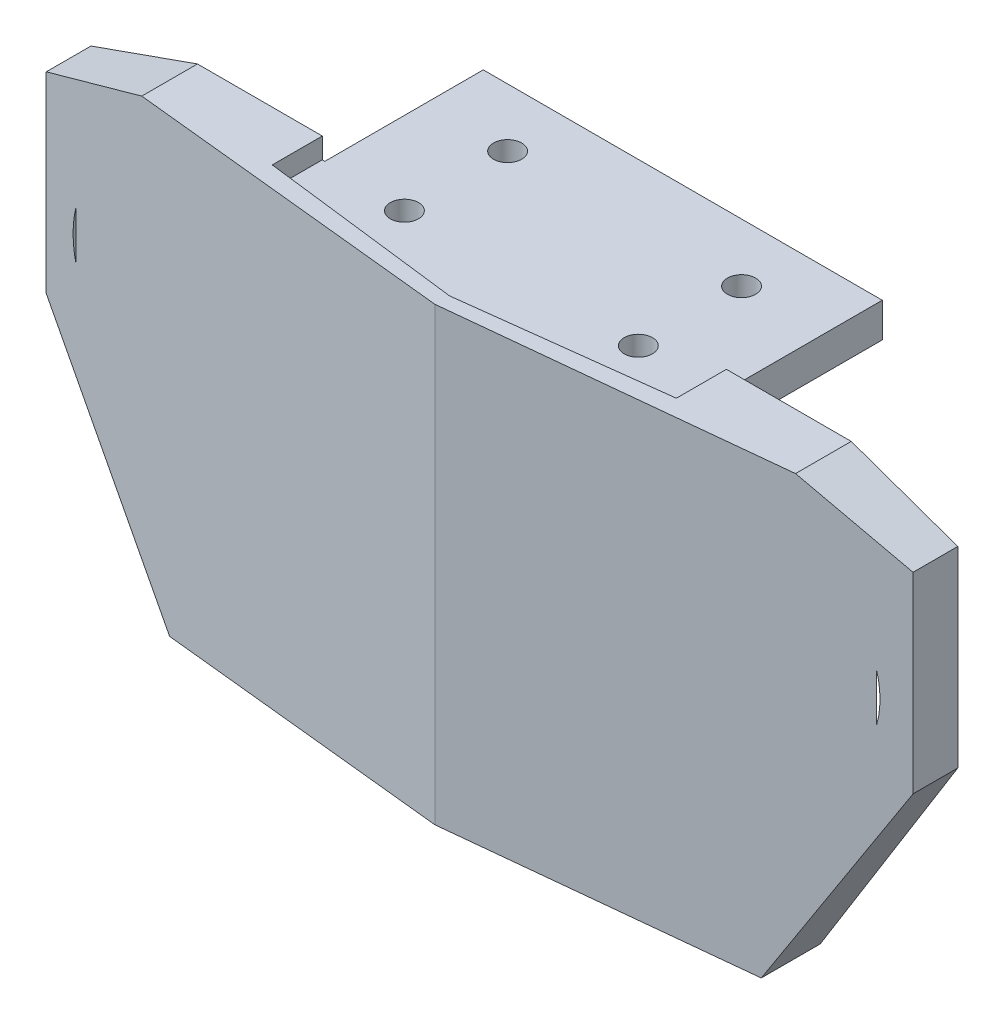
SolidWorks part; units mm, degrees
material "petg 20%"
ref_plane "Front Plane" through (0, 0, 0) normal (0, 0, 1) x (1, 0, 0)
ref_plane "Top Plane" through (0, 0, 0) normal (0, 1, 0) x (1, 0, 0)
ref_plane "Right Plane" through (0, 0, 0) normal (1, 0, 0) x (0, 0, -1)
sketch "Sketch1" plane through (0, 0, 0) normal (0, 0, 1) x (1, 0, 0)
  line L1 (-100, 30) -> (100, 30)
  line L2 (-100, 30) -> (-100, -30)
  line L3 (-100, -30) -> (100, -30)
  line L4 (100, 30) -> (100, -30)
  line L5 (-100, 30) -> (100, -30) construction
  line L6 (-100, -30) -> (100, 30) construction
  point P0 (0, 0)
  dimension "D1" = 200
  dimension "D2" = 60
extrude "Boss-Extrude1" add sketch "Sketch1" along normal blind 25
sketch "Sketch3" plane through (0, 0, 0) normal (0, 0, -1) x (-1, 0, 0)
  circle A0 centre (-45, 0) radius 13.65
  circle A1 centre (45, 0) radius 13.65
  dimension "D1" = 27.3
  dimension "D2" = 27.3
  dimension "D3" = 45
  dimension "D4" = 45
extrude "Cut-Extrude1" cut sketch "Sketch3" against normal blind 7
sketch "Sketch6" plane through (0, 0, 0) normal (0, 0, -1) x (-1, 0, 0)
  line L0 (0, 53.6444) -> (0, -51.0008) construction
  line L1 (-87.0208, 30) -> (-100, 15.5316)
  line L2 (-100, 30) -> (100, 30) construction
  line L3 (-100, -30) -> (-100, 30) construction
  line L4 (-100, -15.0909) -> (-89.0035, -30)
  line L5 (100, -30) -> (-100, -30) construction
  line L9 (100, -15.0909) -> (89.0035, -30)
  line L10 (87.0208, 30) -> (100, 15.5316)
  line L11 (-100, -15.0909) -> (-100, -30)
  line L12 (-100, -30) -> (-89.0035, -30)
  line L15 (-100, 15.5316) -> (-100, 30)
  line L16 (-100, 30) -> (-87.0208, 30)
  line L17 (87.0208, 30) -> (100, 30)
  line L18 (100, 30) -> (100, 15.5316)
  line L19 (89.0035, -30) -> (100, -30)
  line L20 (100, -30) -> (100, -15.0909)
extrude "Cut-Extrude3" cut sketch "Sketch6" against normal through all contours L16 L1 L15 | L12 L4 L11 | L20 L9 L19 | L18 L10 L17
ref_plane "Plane1" through (0, 0, 0) normal (1, 0, 0) x (0, 0, -1)
sketch "Sketch11" plane through (0, 0, 0) normal (0, 0, -1) x (-1, 0, 0)
  line L1 (-87.0208, 30) -> (87.0208, 30) construction
  line L3 (8.0014, 30) -> (-99.0282, 30)
  line L5 (8.0014, 24.58) -> (-99.0282, 24.58)
  line L6 (-99.0282, 30) -> (-99.0282, 24.58)
  line L7 (8.0014, 30) -> (98.3846, 30)
  line L9 (8.0014, 24.58) -> (98.3846, 24.58)
  line L10 (98.3846, 30) -> (98.3846, 24.58)
extrude "Cut-Extrude7" cut sketch "Sketch11" against normal blind 45
fillet "Fillet8" radius 5 8 edges at (100, 0.2203, 25) (94.5018, -22.5455, 25) (0, -30, 25) (-94.5018, -22.5455, 25) (-100, 0.2203, 25) (95.9414, 20.0558, 25) (-95.9414, 20.0558, 25) (0, 24.58, 25)
sketch "Sketch13" plane through (0, 0, 0) normal (0, 0, -1) x (-1, 0, 0)
  line L0 (-63, 23.42) -> (63, 23.42)
  line L1 (-63, 23.42) -> (-63, -18)
  line L2 (63, 23.42) -> (63, -18)
  line L3 (-63, -18) -> (63, -18)
  line L5 (-112.1704, 31.5072) -> (115.5008, 31.5072)
  line L6 (-112.1704, 31.5072) -> (-112.1704, -36.8856)
  line L7 (-112.1704, -36.8856) -> (115.5008, -36.8856)
  line L8 (115.5008, 31.5072) -> (115.5008, -36.8856)
  circle A0 centre (-45, 0) radius 13.65 construction
  circle A1 centre (45, 0) radius 13.65 construction
  dimension "D1" = 18
  dimension "D2" = 18
  dimension "D3" = 18
  dimension "D4" = 23.42
extrude "Cut-Extrude8" cut sketch "Sketch13" against normal through all contours L0 L1 L3 L2 | L6 L5 L8 L7
sketch "Sketch14" plane through (63, 0, 0) normal (1, 0, 0) x (0, 0, -1)
  line L4 (-25, -18) -> (-13, -18)
  line L5 (-25, -18) -> (-25, 23.42)
  line L6 (-13, -18) -> (-13, 23.42)
  line L7 (-25, 23.42) -> (-13, 23.42)
  line L8 (-25, -18) -> (0, -18) construction
  line L9 (-23.2022, 23.42) -> (0, 23.42) construction
  dimension "D1" = 12
extrude "Cut-Extrude9" cut sketch "Sketch14" against normal through all
sketch "Sketch15" plane through (0, 23.42, 0) normal (0, 1, 0) x (1, 0, 0)
  line L0 (-63, -6.5) -> (0, -13)
  line L1 (-63, -13) -> (-63, 0) construction
  line L2 (-63, -13) -> (63, -13) construction
  line L3 (0, -13) -> (63, -6.5)
  line L4 (63, -13) -> (63, 0) construction
  line L5 (-63, -6.5) -> (-63, -13)
  line L6 (-63, -13) -> (0, -13)
  line L7 (63, -13) -> (63, -6.5)
  line M2 (-63, -13) -> (63, -13)
  line M3 (63, -13) -> (63, 0)
extrude "Cut-Extrude10" cut sketch "Sketch15" against normal through all contours L3 M2 M3 | L0 L5 L6 region at (42, 23.42, 10.8333)
sketch "Sketch19" plane through (0, 0, 0) normal (0, 0, -1) x (-1, 0, 0)
  line L0 (-63, -18) -> (-63, -42.1057)
  line L1 (63, -18) -> (63, -42.1057)
  line L2 (63, -42.1057) -> (-63, -42.1057)
  line L7 (-63, -18) -> (63, -18)
  line L8 (63, -18) -> (63, 23.42)
  line L9 (63, 23.42) -> (-63, 23.42)
  line L10 (-63, 23.42) -> (-63, -18)
  line L11 (-63, -18) -> (63, -18)
  dimension "D1" = 0
extrude "Boss-Extrude2" add sketch "Sketch19" against normal blind 13
sketch "Sketch20" plane through (0, -18, 0) normal (0, 1, 0) x (1, 0, 0)
  line L0 (-63, -6.5) -> (-63, -13)
  line L1 (-63, -13) -> (63, -13)
  line L2 (63, -13) -> (63, -6.5)
  line L3 (63, -6.5) -> (0, -13)
  line L4 (0, -13) -> (-63, -6.5)
  line M1 (0, -13) -> (-63, -6.5)
  line M2 (-63, -6.5) -> (-63, -13)
  line M3 (-63, -13) -> (0, -13)
extrude "Cut-Extrude11" cut sketch "Sketch20" against normal through all contours M3 M1 M2 | L2 L3 L1 region at (-42, -18, 10.8333) region at (42, -18, 10.8333)
sketch "Sketch21" plane through (0, 0, 0) normal (0, 0, -1) x (-1, 0, 0)
  line L0 (-63, -9.958) -> (-43, -42.1057)
  line L1 (-63, 23.42) -> (-63, -42.1057) construction
  line L2 (-63, -42.1057) -> (63, -42.1057) construction
  line L3 (-43, -42.1057) -> (-63, -42.1057)
  line L4 (-63, -42.1057) -> (-63, -9.958)
  line L5 (-47.516, 23.42) -> (-63, 17.936)
  line L6 (-63, 23.42) -> (63, 23.42) construction
  line L7 (-63, 17.936) -> (-63, 23.42)
  line L8 (-63, 23.42) -> (-47.516, 23.42)
  dimension "D1" = 20
extrude "Cut-Extrude12" cut sketch "Sketch21" against normal blind 13
mirror "Mirror1" about plane through (0, 0, 0) normal (1, 0, 0) of "Cut-Extrude12"
sketch "Sketch22" plane through (0, 23.42, 0) normal (0, 1, 0) x (1, 0, 0)
  line L0 (-29, 0) -> (29, 0)
  line L1 (-29, 0) -> (-29, 23.0258)
  line L2 (29, 0) -> (29, 23.0258)
  line L3 (-29, 23.0258) -> (29, 23.0258)
  line L4 (47.516, 0) -> (-47.516, 0) construction
  line L5 (-63, -6.5) -> (-63, 0) construction
  line L6 (63, -6.5) -> (63, 0) construction
  dimension "D1" = 34
  dimension "D2" = 34
extrude "Boss-Extrude3" add sketch "Sketch22" against normal blind 8
ref_plane "Plane2" through (0, -9.3429, 0) normal (0, -1, 0) x (-1, 0, 0)
mirror "Mirror2" about plane through (0, -9.3429, 0) normal (0, -1, 0) of "Boss-Extrude3"
sketch "Sketch24" plane through (0, 0, 0) normal (0, 0, -1) x (-1, 0, 0)
  line L0 (-20, 15.42) -> (20, 15.42)
  line L1 (-20, 15.42) -> (-20, -34.1057)
  line L2 (20, 15.42) -> (20, -34.1057)
  line L3 (-20, -34.1057) -> (20, -34.1057)
  line L4 (-29, -34.1057) -> (29, -34.1057) construction
  line L5 (29, 15.42) -> (-29, 15.42) construction
  dimension "D1" = 20
  dimension "D2" = 20
  dimension "D3" = 0
  dimension "D4" = 0
extrude "Cut-Extrude13" cut sketch "Sketch24" against normal blind 4
sketch "Sketch25" plane through (0, 23.42, 0) normal (0, 1, 0) x (1, 0, 0)
  line L0 (0, -10.8758) -> (-29.3702, -7.2738)
  line L1 (0, -55) -> (0, 55) construction
  line L2 (-29.3702, -7.2738) -> (-29.3702, 0)
  line L3 (-29.3702, 0) -> (-29, 0)
  line L4 (-29, 0) -> (-29, 23.0258)
  line L5 (29, 0) -> (29, 23.0258)
  line L6 (29.3702, -7.2738) -> (29.3702, 0)
  line L7 (29.3702, 0) -> (29, 0)
  line L8 (0, -10.8758) -> (29.3702, -7.2738)
  line L9 (-29, 23.0258) -> (-29, 0) construction
  line L11 (47.516, 0) -> (29, 0) construction
  point P14 (29.1851, 0)
extrude "Cut-Extrude14" cut sketch "Sketch25" against normal blind 3 and the other way through all
sketch "Sketch26" plane through (0, -42.1057, 0) normal (0, -1, 0) x (1, 0, 0)
  line L0 (-29.37, 7.8486) -> (-29.37, 0)
  line L2 (-29, 0) -> (-29.37, 0)
  line L3 (-29, 0) -> (-29, -23.0258)
  line L4 (-29.37, 7.8486) -> (0, 10.8788)
  line L5 (0, -55) -> (0, 55) construction
  line L6 (0, 13) -> (-43, 8.5635) construction
  line L7 (29, 0) -> (29, -23.0258)
  line L8 (29, 0) -> (29.37, 0)
  line L9 (29.37, 7.8486) -> (29.37, 0)
  line L10 (29.37, 7.8486) -> (0, 10.8788)
  line L11 (-29, 0) -> (-43, 0) construction
  dimension "D1" = 2.11
  dimension "D2" = 58.74
extrude "Cut-Extrude15" cut sketch "Sketch26" against normal blind 3 and the other way through all
sketch "Sketch27" plane through (0, 20.42, 0) normal (0, 1, 0) x (1, 0, 0)
  circle A0 centre (17, -0.4338) radius 2.05
  circle A1 centre (-17, -0.4338) radius 2.05
  circle A2 centre (-17, 14.5662) radius 2.05
  circle A3 centre (17, 14.5662) radius 2.05
extrude "Cut-Extrude16" cut sketch "Sketch27" against normal through all
